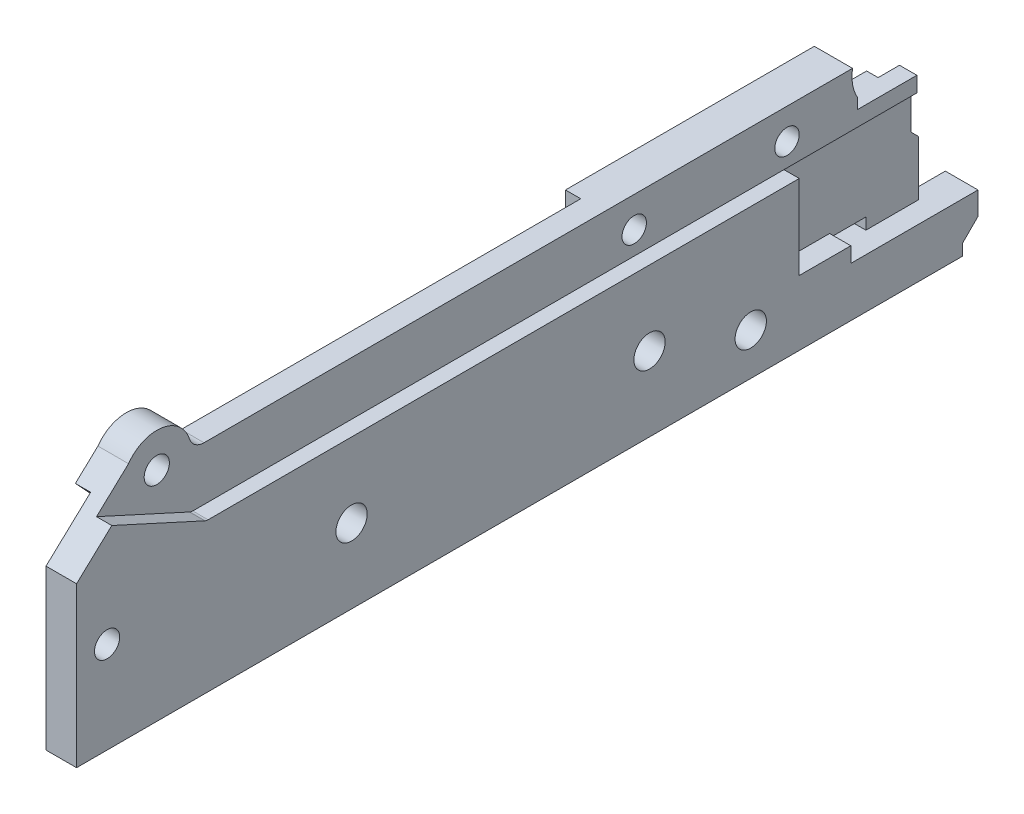
SolidWorks part; units mm, degrees
ref_plane "前视基准面" through (0, 0, 0) normal (0, 0, 1) x (1, 0, 0)
ref_plane "上视基准面" through (0, 0, 0) normal (0, 1, 0) x (1, 0, 0)
ref_plane "右视基准面" through (0, 0, 0) normal (1, 0, 0) x (0, 0, -1)
other "Configuration Table"
sketch "草图1" plane through (0, 0, 0) normal (1, 0, 0) x (0, 0, -1)
  line L0 (0, 0) -> (20, 0) construction
  line L2 (29.2, 6.5) -> (-4, 6.5)
  line L3 (29.2, 6.5) -> (29.2, -15.5)
  line L4 (29.2, -15.5) -> (-4, -15.5)
  line L5 (-4, 6.5) -> (-4, -15.5)
  circle A0 centre (0, 0) radius 1.6
  circle A1 centre (20, 0) radius 1.6
  dimension "D1" = 20
  dimension "D2" = 3.2
  dimension "D4" = 9.2
  dimension "D6" = 4
  dimension "D3" = 6.5
  dimension "D5" = 22
extrude "凸台-拉伸1" add sketch "草图1" along normal blind 7
sketch "草图2" plane through (7, 0, 0) normal (1, 0, 0) x (0, 0, -1)
  line L1 (-4, 6.5) -> (29.2, 6.5)
  line L2 (-4, 6.5) -> (-4, 17)
  line L3 (-4, 17) -> (29.2, 17)
  line L4 (29.2, 6.5) -> (29.2, 17)
  dimension "D1" = 10.5
extrude "凸台-拉伸2" add sketch "草图2" against normal offset from surface (2 mm away) 5 up to face at (0, 0, -1.6)
sketch "草图3" plane through (0, 0, 4) normal (0, 0, 1) x (1, 0, 0)
  line L1 (7, -15.5) -> (1, -15.5)
  line L2 (7, -15.5) -> (7, 6.5)
  line L3 (7, 6.5) -> (3, 6.5)
  line L4 (1, -15.5) -> (1, 4.5)
  line L5 (3, 6.5) -> (3, 4.5)
  line L6 (3, 4.5) -> (1, 4.5)
  line L7 (5, 6.5) -> (0, 6.5) construction
  dimension "D1" = 6
  dimension "D2" = 2
  dimension "D3" = 2
extrude "凸台-拉伸3" add sketch "草图3" along normal blind 60
sketch "草图4" plane through (0, 0, 4) normal (0, 0, 1) x (1, 0, 0)
  line L4 (5, 6.5) -> (7, 6.5)
  line L5 (7, 6.5) -> (7, 17)
  line L6 (7, 17) -> (5, 17)
  line L7 (5, 17) -> (5, 6.5)
  line L8 (5, 6.5) -> (7, 6.5)
  line L9 (7, 6.5) -> (7, 17)
  line L10 (7, 17) -> (5, 17)
  line L11 (5, 17) -> (5, 6.5)
  dimension "D1" = 0
extrude "凸台-拉伸4" add sketch "草图4" along normal blind 38.5
sketch "草图5" plane through (0, 0, 42.5) normal (0, 0, 1) x (1, 0, 0)
  line L0 (7, 6.5) -> (7, 17) construction
  line L1 (7, 6.5) -> (3, 6.5)
  line L2 (7, 6.5) -> (7, 17)
  line L3 (7, 17) -> (3, 17)
  line L4 (3, 6.5) -> (3, 17)
  line L5 (7, 17) -> (5, 17) construction
extrude "凸台-拉伸5" add sketch "草图5" along normal blind 2
sketch "草图6" plane through (0, 0, 44.5) normal (0, 0, 1) x (1, 0, 0)
  line L4 (7, 6.5) -> (7, 17)
  line L5 (7, 17) -> (3, 17)
  line L6 (3, 17) -> (3, 6.5)
  line L7 (3, 6.5) -> (7, 6.5)
  line L8 (7, 6.5) -> (7, 17)
  line L9 (7, 17) -> (3, 17)
  line L10 (3, 17) -> (3, 6.5)
  line L11 (3, 6.5) -> (7, 6.5)
  dimension "D1" = 0
extrude "凸台-拉伸6" add sketch "草图6" along normal up to surface (19.5 mm away) up to face at (3.6667, -1.5, 64)
sketch "草图7" plane through (0, 17, 0) normal (0, 1, 0) x (1, 0, 0)
  line L0 (1, -64) -> (1, -4) construction
  line L1 (7, 29.2) -> (1, 29.2)
  line L2 (7, 29.2) -> (7, -64)
  line L3 (7, -64) -> (1, -64)
  line L4 (1, 29.2) -> (1, -64)
  line L5 (7, -64) -> (3, -64) construction
extrude "凸台-拉伸7" add sketch "草图7" along normal blind 2
sketch "草图8" plane through (1, 0, 0) normal (-1, 0, 0) x (0, 0, 1)
  line L1 (-29.2, 19) -> (64, 19)
  line L2 (-29.2, 19) -> (-29.2, 24)
  line L3 (-29.2, 24) -> (64, 24)
  line L4 (64, 19) -> (64, 24)
  dimension "D1" = 5
extrude "凸台-拉伸8" add sketch "草图8" against normal blind 3
sketch "草图10" plane through (1, 0, 0) normal (-1, 0, 0) x (0, 0, 1)
  line L1 (-29.2, 24) -> (64, 24)
  line L2 (-29.2, 24) -> (-29.2, 22)
  line L3 (-29.2, 22) -> (64, 22)
  line L4 (64, 24) -> (64, 22)
  line L5 (64, 24) -> (64, 17) construction
  dimension "D1" = 2
extrude "凸台-拉伸9" add sketch "草图10" along normal blind 5.5
sketch "草图12" plane through (-4.5, 0, 0) normal (-1, 0, 0) x (0, 0, 1)
  line L0 (64, 24) -> (-29.2, 24) construction
  line L1 (-29.2, 22) -> (-11.2, 22)
  line L2 (-29.2, 22) -> (-29.2, 24)
  line L3 (-29.2, 24) -> (-11.2, 24)
  line L4 (-11.2, 22) -> (-11.2, 24)
  dimension "D1" = 18
extrude "切除-拉伸1" cut sketch "草图12" against normal up to surface (5.5 mm away) up to face at (1, 19.5, 17.4)
sketch "草图13" plane through (1, 0, 0) normal (-1, 0, 0) x (0, 0, 1)
  line L0 (-11.2, 22) -> (64, 22) construction
  line L1 (10.8, 22) -> (-29.2, 22)
  line L2 (10.8, 22) -> (10.8, 17)
  line L3 (10.8, 17) -> (-29.2, 17)
  line L4 (-29.2, 22) -> (-29.2, 17)
  dimension "D1" = 40
extrude "凸台-拉伸10" add sketch "草图13" along normal blind 3.5
sketch "草图14" plane through (-2.5, 0, 0) normal (-1, 0, 0) x (0, 0, 1)
  line L0 (-29.2, 17) -> (10.8, 17) construction
  line L1 (-11.2, 19.8) -> (-9.2, 19.8)
  line L2 (-11.2, 19.8) -> (-11.2, 17)
  line L3 (-11.2, 17) -> (-9.2, 17)
  line L4 (-9.2, 19.8) -> (-9.2, 17)
  line L5 (10.8, 22) -> (-11.2, 22) construction
  line L6 (-11.2, 22) -> (-11.2, 24) construction
  dimension "D1" = 2
  dimension "D2" = 2.2
sketch "草图15" plane through (4, 0, 0) normal (1, 0, 0) x (0, 0, -1)
  line L0 (29.2, 19) -> (-64, 19) construction
  line L1 (29.2, 24) -> (13.7, 24)
  line L2 (29.2, 24) -> (29.2, 19)
  line L3 (29.2, 19) -> (13.7, 19)
  line L4 (13.7, 24) -> (13.7, 19)
  line L6 (11.2, 22) -> (11.2, 24) construction
  dimension "D1" = 2.5
extrude "切除-拉伸2" cut sketch "草图15" against normal up to next
sketch "草图16" plane through (0, 22, 0) normal (0, 1, 0) x (1, 0, 0)
  line L4 (1, 11.2) -> (1, 13.7)
  line L5 (1, 13.7) -> (-2.5, 13.7)
  line L6 (-2.5, 13.7) -> (-2.5, 11.2)
  line L7 (-2.5, 11.2) -> (1, 11.2)
  line L8 (1, 11.2) -> (1, 13.7)
  line L9 (1, 13.7) -> (-2.5, 13.7)
  line L10 (-2.5, 13.7) -> (-2.5, 11.2)
  line L11 (-2.5, 11.2) -> (1, 11.2)
  dimension "D1" = 0
extrude "凸台-拉伸12" add sketch "草图16" along normal up to surface (2 mm away) up to face at (0.1667, 24, 13.0333)
sketch "草图17" plane through (7, 0, 0) normal (1, 0, 0) x (0, 0, -1)
  line L0 (-47.5, 24) -> (-64, 8.6135)
  line L1 (-64, 24) -> (13.7, 24) construction
  line L2 (-64, -15.5) -> (-64, 19) construction
  line L3 (-64, 8.6135) -> (-64, 24)
  line L4 (-64, 24) -> (-47.5, 24)
  dimension "D1" = 133
  dimension "D2" = 16.5
extrude "切除-拉伸3" cut sketch "草图17" against normal up to next
chamfer "倒角1" distance 3.5 angle 45 1 edges at (-4.5, 23, 48.5724)
sketch "草图18" plane through (-2.5, 0, 0) normal (-1, 0, 0) x (0, 0, 1)
  line L0 (-13.7, 19) -> (-13.7, 24) construction
  line L1 (-29.2, 19) -> (-13.7, 19) construction
  line L2 (-11.337, 27.2) -> (-11.337, 24)
  line L3 (-13.7, 24) -> (-11.2, 24) construction
  line L4 (-11.337, 24) -> (-13.7, 24)
  line L5 (-13.7, 24) -> (-13.7, 19)
  line L6 (-13.7, 19) -> (-21.337, 19)
  line L7 (-21.337, 19) -> (-21.337, 27.2)
  circle A0 centre (-16.337, 27.2) radius 1.65
  arc A1 (-11.337, 27.2) -> (-21.337, 27.2) centre (-16.337, 27.2) ccw
  dimension "D1" = 2.637
  dimension "D2" = 8.2
  dimension "D3" = 3.3
  dimension "D4" = 10
extrude "凸台-拉伸13" add sketch "草图18" against normal blind 2
fillet "圆角1" radius 2 2 edges at (-1.5, 24, -11.337) (-1.5, 19, -21.337)
sketch "草图19" plane through (0, 24, 0) normal (0, 1, 0) x (1, 0, 0)
  line L0 (-0.5, 9.337) -> (-0.5, 11.337) construction
  line L1 (4, 13.7) -> (-0.5, 13.7)
  line L2 (4, 13.7) -> (4, -7.8)
  line L3 (4, -7.8) -> (-0.5, -7.8)
  line L4 (-0.5, 13.7) -> (-0.5, -7.8)
  line L5 (-2.5, -10.8) -> (1, -10.8) construction
  dimension "D1" = 3
extrude "切除-拉伸4" cut sketch "草图19" against normal up to surface (5 mm away) up to face at (2, 19, -3.3438)
chamfer "倒角2" distance 3 angle 45 2 edges at (4, 24, 27.65) (1, 22, 30.2224)
sketch "草图20" plane through (7, 0, 0) normal (1, 0, 0) x (0, 0, -1)
  line L0 (-64, -15.5) -> (-64, 8.6135) construction
  line L1 (-64, -15.5) -> (29.2, -15.5) construction
  circle A0 centre (-62.5, 4) radius 1.65
  dimension "D1" = 1.5
  dimension "D2" = 19.5
  dimension "D3" = 3.3
extrude "切除-拉伸5" cut sketch "草图20" against normal up to next
sketch "草图21" plane through (1, 0, 0) normal (-1, 0, 0) x (0, 0, 1)
  circle A0 centre (62.5, 4) radius 1.65
  circle A1 centre (62.5, 4) radius 4.5
  dimension "D1" = 9
extrude "凸台-拉伸14" add sketch "草图21" against normal up to surface (6 mm away) up to face at (7, 3.3734, 35.3303)
sketch "草图22" plane through (1, 0, 0) normal (-1, 0, 0) x (0, 0, 1)
  line L3 (66.1986, 6.5633) -> (75, -1.6442)
  line L4 (75, -1.6442) -> (75, -15.5)
  line L5 (75, -15.5) -> (64, -15.5)
  line L6 (55.0066, 17) -> (64, 8.6135) construction
  line L7 (64, -0.2426) -> (64, -15.5)
  circle A2 centre (62.5, 4) radius 1.65 construction
  arc A3 (64, -0.2426) -> (58.0279, 4.5) centre (62.5, 4) ccw construction
  arc A4 (64, -0.2426) -> (66.1986, 6.5633) centre (62.5, 4) ccw
  dimension "D1" = 12.5
extrude "凸台-拉伸15" add sketch "草图22" against normal up to surface (6 mm away) up to face at (7, 3.3734, 36.2088)
sketch "草图23" plane through (7, 0, 0) normal (1, 0, 0) x (0, 0, -1)
  line L0 (-64, 8.6135) -> (-64.799, 7.8684)
  line L1 (-64.799, 7.8684) -> (-64, 8.2426)
  line L2 (-64, 8.2426) -> (-64, 8.6135)
  line L3 (-64, 8.6135) -> (-52.8618, 19) construction
  arc A0 (-64, 8.2426) -> (-66.1986, 6.5633) centre (-62.5, 4) ccw construction
extrude "凸台-拉伸16" add sketch "草图23" against normal up to surface (4 mm away) up to face at (3, 9.2872, 41.6414)
sketch "草图24" plane through (1, 0, 0) normal (-1, 0, 0) x (0, 0, 1)
  line L0 (75, -15.5) -> (75, -1.6442) construction
  line L1 (75, -15.5) -> (4, -15.5) construction
  circle A0 centre (71, -10.5) radius 1.65
  dimension "D1" = 3.3
  dimension "D2" = 4
  dimension "D3" = 5
extrude "切除-拉伸6" cut sketch "草图24" against normal up to next
sketch "草图25" plane through (5, 0, 0) normal (-1, 0, 0) x (0, 0, 1)
  line L0 (-29.2, 11.75) -> (42.5, 11.75) construction
  line L1 (-29.2, 6.5) -> (-29.2, 17) construction
  line L2 (42.5, 17) -> (42.5, 6.5) construction
  line L3 (17.8, 11.75) -> (-14.2, 11.75) construction
  line L4 (17.8, 8) -> (-14.2, 8)
  line L5 (17.8, 15.5) -> (-14.2, 15.5)
  arc A0 (17.8, 8) -> (17.8, 15.5) centre (17.8, 11.75) ccw
  arc A1 (-14.2, 15.5) -> (-14.2, 8) centre (-14.2, 11.75) ccw
  point P8 (1.8, 11.75)
  dimension "D1" = 47
  dimension "D2" = 15
  dimension "D3" = 7.5
extrude "切除-拉伸7" cut sketch "草图25" against normal up to next
sketch "草图26" plane through (0, 0, 42.5) normal (0, 0, -1) x (-1, 0, 0)
  line L4 (-5, 17) -> (-5, 6.5)
  line L5 (-5, 6.5) -> (-3, 6.5)
  line L6 (-3, 6.5) -> (-3, 17)
  line L7 (-3, 17) -> (-5, 17)
  line L8 (-5, 17) -> (-5, 6.5)
  line L9 (-5, 6.5) -> (-3, 6.5)
  line L10 (-3, 6.5) -> (-3, 17)
  line L11 (-3, 17) -> (-5, 17)
  dimension "D1" = 0
extrude "切除-拉伸8" cut sketch "草图26" against normal blind 5
sketch "草图27" plane through (0, 0, 4) normal (0, 0, 1) x (1, 0, 0)
  line L1 (1, 4.5) -> (3, 4.5)
  line L2 (1, 4.5) -> (1, 6.5)
  line L3 (1, 6.5) -> (3, 6.5)
  line L4 (3, 4.5) -> (3, 6.5)
extrude "凸台-拉伸17" add sketch "草图27" along normal blind 10
sketch "草图28" plane through (1, 0, 0) normal (-1, 0, 0) x (0, 0, 1)
  line L0 (67, 1.4943) -> (67, -15.5)
  line L2 (75, -15.5) -> (4, -15.5) construction
  line L3 (67, -15.5) -> (75, -15.5)
  line L4 (75, -15.5) -> (75, -1.6442)
  line L5 (75, -1.6442) -> (69.1556, 3.8058)
  line L6 (69.1556, 3.8058) -> (67, 1.4943)
  line L7 (75, -1.6442) -> (66.1986, 6.5633) construction
  circle A0 centre (62.5, 4) radius 1.65 construction
  dimension "D3" = 5
  dimension "D1" = 8
  dimension "D2" = 137
extrude "切除-拉伸9" cut sketch "草图28" against normal blind 2
sketch "草图29" plane through (7, 0, 0) normal (1, 0, 0) x (0, 0, -1)
  circle A0 centre (34, 3.1) radius 5.5
  circle A1 centre (20, 0) radius 1.6 construction
  dimension "D1" = 3.1
  dimension "D2" = 14
  dimension "D3" = 11
extrude "切除-拉伸10" cut sketch "草图29" against normal up to next
sketch "草图30" plane through (1, 0, 0) normal (-1, 0, 0) x (0, 0, 1)
  line L0 (4, 6.5) -> (4, -15.5) construction
  line L1 (4, -4.5) -> (67, -4.5)
  line L2 (4, -4.5) -> (4, -6.5)
  line L3 (4, -6.5) -> (67, -6.5)
  line L4 (67, -4.5) -> (67, -6.5)
  line L5 (67, 1.4943) -> (67, -15.5) construction
  circle A0 centre (0, 0) radius 1.6 construction
  dimension "D1" = 4.5
  dimension "D2" = 2
extrude "凸台-拉伸18" add sketch "草图30" along normal up to surface (1 mm away) up to face at (0, -1.9667, -18.0167)
sketch "草图31" plane through (5, 0, 0) normal (-1, 0, 0) x (0, 0, 1)
  line L0 (-14.2, 8) -> (17.8, 8) construction
  line L1 (17.8, 15.5) -> (-14.2, 15.5) construction
  line L2 (-14.2, 8) -> (17.8, 8)
  line L3 (17.8, 15.5) -> (-14.2, 15.5)
  line L4 (-29.2, 6.5) -> (47.5, 6.5)
  line L5 (47.5, 6.5) -> (47.5, 17)
  line L6 (47.5, 17) -> (-29.2, 17)
  line L7 (-29.2, 17) -> (-29.2, 6.5)
  line L8 (-29.2, 6.5) -> (47.5, 6.5)
  line L9 (47.5, 6.5) -> (47.5, 17)
  line L10 (47.5, 17) -> (-29.2, 17)
  line L11 (-29.2, 17) -> (-29.2, 6.5)
  arc A0 (17.8, 8) -> (17.8, 15.5) centre (17.8, 11.75) ccw construction
  arc A1 (-14.2, 15.5) -> (-14.2, 8) centre (-14.2, 11.75) ccw construction
  arc A2 (17.8, 8) -> (17.8, 15.5) centre (17.8, 11.75) ccw
  arc A3 (-14.2, 15.5) -> (-14.2, 8) centre (-14.2, 11.75) ccw
  dimension "D1" = 0
sketch "草图32" plane through (-2.5, 0, 0) normal (-1, 0, 0) x (0, 0, 1)
  line L8 (-11.2, 22) -> (-11.2, 25.2725)
  line L9 (-11.337, 26) -> (-11.337, 27.2)
  line L10 (-21.337, 27.2) -> (-21.337, 21)
  line L11 (-23.337, 19) -> (-29.2, 19)
  line L12 (-29.2, 19) -> (-29.2, 17)
  line L13 (-29.2, 17) -> (10.8, 17)
  line L14 (10.8, 17) -> (10.8, 22)
  line L15 (10.8, 22) -> (-11.2, 22)
  line L16 (-11.2, 22) -> (-11.2, 25.2725)
  line L17 (-11.337, 26) -> (-11.337, 27.2)
  line L18 (-21.337, 27.2) -> (-21.337, 21)
  line L19 (-23.337, 19) -> (-29.2, 19)
  line L20 (-29.2, 19) -> (-29.2, 17)
  line L21 (-29.2, 17) -> (10.8, 17)
  line L22 (10.8, 17) -> (10.8, 22)
  line L23 (10.8, 22) -> (-11.2, 22)
  circle A0 centre (-16.337, 27.2) radius 1.65 construction
  circle A1 centre (-16.337, 27.2) radius 1.65
  arc A3 (-11.337, 26) -> (-11.2, 25.2725) centre (-9.337, 26) ccw
  arc A4 (-11.337, 27.2) -> (-21.337, 27.2) centre (-16.337, 27.2) ccw
  arc A5 (-23.337, 19) -> (-21.337, 21) centre (-23.337, 21) ccw
  arc A6 (-11.337, 26) -> (-11.2, 25.2725) centre (-9.337, 26) ccw
  arc A7 (-11.337, 27.2) -> (-21.337, 27.2) centre (-16.337, 27.2) ccw
  arc A8 (-23.337, 19) -> (-21.337, 21) centre (-23.337, 21) ccw
  dimension "D1" = 0
extrude "凸台-拉伸19" add sketch "草图32" along normal blind 0.775
sketch "草图34" plane through (0, -15.5, 0) normal (0, -1, 0) x (1, 0, 0)
  line L8 (3, 75) -> (3, 67)
  line L9 (3, 67) -> (1, 67)
  line L10 (1, 67) -> (1, 4)
  line L11 (1, 4) -> (0, 4)
  line L12 (0, 4) -> (0, -29.2)
  line L13 (0, -29.2) -> (7, -29.2)
  line L14 (7, -29.2) -> (7, 75)
  line L15 (7, 75) -> (3, 75)
  line L16 (3, 75) -> (3, 67)
  line L17 (3, 67) -> (1, 67)
  line L18 (1, 67) -> (1, 4)
  line L19 (1, 4) -> (0, 4)
  line L20 (0, 4) -> (0, -29.2)
  line L21 (0, -29.2) -> (7, -29.2)
  line L22 (7, -29.2) -> (7, 75)
  line L23 (7, 75) -> (3, 75)
  dimension "D1" = 0
extrude "凸台-拉伸20" add sketch "草图34" along normal blind 5.5
sketch "草图35" plane through (0, 0, 0) normal (-1, 0, 0) x (0, 0, 1)
  line L1 (-24.2, -11) -> (-29.2, -11)
  line L2 (-24.2, -11) -> (-24.2, -21)
  line L3 (-24.2, -21) -> (-29.2, -21)
  line L4 (-29.2, -11) -> (-29.2, -21)
  dimension "D1" = 5
  dimension "D2" = 10
extrude "切除-拉伸12" cut sketch "草图35" against normal blind 1.225
sketch "草图36" plane through (0, 0, -29.2) normal (0, 0, -1) x (-1, 0, 0)
  line L1 (-1.225, -21) -> (-5.225, -21)
  line L2 (-1.225, -21) -> (-1.225, -11)
  line L3 (-1.225, -11) -> (-5.225, -11)
  line L4 (-5.225, -21) -> (-5.225, -11)
  dimension "D1" = 10
  dimension "D2" = 4
extrude "凸台-拉伸21" add sketch "草图36" along normal blind 5
sketch "草图37" plane through (5.225, 0, 0) normal (1, 0, 0) x (0, 0, -1)
  line L0 (34.2, -11) -> (34.2, -21) construction
  line L1 (33.6, -16) -> (28.85, -16)
  line L2 (33.6, -16) -> (33.6, -13)
  line L3 (33.6, -13) -> (28.85, -13)
  line L4 (28.85, -16) -> (28.85, -13)
  line L5 (34.2, -21) -> (29.2, -21) construction
  dimension "D1" = 5
  dimension "D2" = 3
  dimension "D3" = 5.35
  dimension "D4" = 0.6
extrude "切除-拉伸13" cut sketch "草图37" against normal up to next and the other way up to next
sketch "草图38" plane through (5.225, 0, 0) normal (1, 0, 0) x (0, 0, -1)
  line L0 (34.2, -11) -> (34.2, -21) construction
  line L1 (34.2, -14) -> (19.6, -14)
  line L2 (34.2, -14) -> (34.2, -3)
  line L3 (34.2, -3) -> (19.6, -3)
  line L4 (19.6, -14) -> (19.6, -3)
  line L5 (33.6, -16) -> (29.2, -16) construction
  line L7 (28.85, -16) -> (28.85, -13) construction
  dimension "D1" = 2
  dimension "D2" = 9.25
  dimension "D3" = 11
extrude "切除-拉伸14" cut sketch "草图38" along normal up to next and the other way blind 1
sketch "草图39" plane through (0, 0, -34.2) normal (0, 0, -1) x (-1, 0, 0)
  line L1 (-2.725, -1) -> (-4.225, -1)
  line L2 (-2.725, -1) -> (-2.725, -21)
  line L3 (-2.725, -21) -> (-4.225, -21)
  line L4 (-4.225, -1) -> (-4.225, -21)
  line L5 (-5.225, -21) -> (-1.225, -21) construction
  line L6 (-5.225, -14) -> (-5.225, -21) construction
  line L7 (-1.225, -11) -> (0, -11) construction
  dimension "D1" = 2.5
  dimension "D2" = 1
  dimension "D3" = 10
extrude "凸台-拉伸22" add sketch "草图39" along normal blind 5.8 and the other way up to next
sketch "草图40" plane through (0, 0, -29.2) normal (0, 0, -1) x (-1, 0, 0)
  line L1 (-1.225, -11) -> (-2.725, -11)
  line L2 (-1.225, -11) -> (-1.225, -1)
  line L3 (-1.225, -1) -> (-2.725, -1)
  line L4 (-2.725, -11) -> (-2.725, -1)
extrude "凸台-拉伸23" add sketch "草图40" along normal up to surface (5 mm away) up to face at (1.975, -16, -34.2)
sketch "草图41" plane through (4.225, 0, 0) normal (1, 0, 0) x (0, 0, -1)
  line L1 (40, -1) -> (39, -1)
  line L2 (40, -1) -> (40, -8)
  line L3 (40, -8) -> (39, -8)
  line L4 (39, -1) -> (39, -8)
  dimension "D1" = 1
  dimension "D2" = 7
extrude "切除-拉伸15" cut sketch "草图41" against normal up to next
chamfer "倒角3" distance 1 angle 45 1 edges at (3.475, -8, -39)
sketch "草图42" plane through (0, 0, -29.2) normal (0, 0, -1) x (-1, 0, 0)
  line L1 (-4.225, -21) -> (-7, -21)
  line L2 (-4.225, -21) -> (-4.225, -16)
  line L3 (-4.225, -16) -> (-7, -16)
  line L4 (-7, -21) -> (-7, -16)
extrude "凸台-拉伸24" add sketch "草图42" along normal up to surface (10.8 mm away) up to face at (3.475, -14.5, -40)
sketch "草图43" plane through (4.225, 0, 0) normal (1, 0, 0) x (0, 0, -1)
  line L4 (33.6, -16) -> (34.2, -16)
  line L5 (34.2, -16) -> (34.2, -14)
  line L6 (34.2, -14) -> (33.6, -14)
  line L7 (33.6, -14) -> (33.6, -16)
  line L8 (33.6, -16) -> (34.2, -16)
  line L9 (34.2, -16) -> (34.2, -14)
  line L10 (34.2, -14) -> (33.6, -14)
  line L11 (33.6, -14) -> (33.6, -16)
  dimension "D1" = 0
extrude "切除-拉伸16" cut sketch "草图43" along normal up to next
sketch "草图44" plane through (4.225, 0, 0) normal (1, 0, 0) x (0, 0, -1)
  line L1 (29.2, -3) -> (39, -3)
  line L2 (29.2, -3) -> (29.2, -1)
  line L3 (29.2, -1) -> (39, -1)
  line L4 (39, -3) -> (39, -1)
extrude "凸台-拉伸25" add sketch "草图44" along normal offset from surface (2 mm away) 0.775 up to face at (7, 0, -21.6)
sketch "草图45" plane through (7, 0, 0) normal (1, 0, 0) x (0, 0, -1)
  line L0 (39, -3) -> (19.6, -3) construction
  line L1 (28.5, 3.1) -> (29.3, 3.1)
  line L2 (28.5, 3.1) -> (28.5, -3)
  line L3 (28.5, -3) -> (29.3, -3)
  line L4 (29.3, 3.1) -> (29.3, -3)
  arc A0 (29.2, 5.7851) -> (29.2, 0.4149) centre (34, 3.1) ccw construction
extrude "切除-拉伸17" cut sketch "草图45" against normal up to surface (0.775 mm away) up to face at (6.225, -2, -34.1)
sketch "草图46" plane through (7, 0, 0) normal (1, 0, 0) x (0, 0, -1)
  circle A0 centre (13.25, -17) radius 2.05
  circle A1 centre (20, 0) radius 1.6 construction
  dimension "D1" = 17
  dimension "D2" = 6.75
  dimension "D3" = 4.1
extrude "切除-拉伸18" cut sketch "草图46" against normal up to next
sketch "草图47" plane through (1, 0, 0) normal (-1, 0, 0) x (0, 0, 1)
  line L0 (62.5, -0.5) -> (67, -0.5)
  line L8 (4, -4.5) -> (67, -4.5)
  line L9 (67, -4.5) -> (67, 1.4943)
  line L10 (67, 1.4943) -> (69.1556, 3.8058)
  line L11 (69.1556, 3.8058) -> (66.1986, 6.5633)
  line L12 (58.0279, 4.5) -> (14, 4.5)
  line L13 (14, 4.5) -> (14, 6.5)
  line L14 (14, 6.5) -> (4, 6.5)
  line L15 (4, 6.5) -> (4, -4.5)
  line L16 (4, -4.5) -> (67, -4.5)
  line L17 (67, -4.5) -> (67, -0.5)
  line L20 (58.0279, 4.5) -> (14, 4.5)
  line L21 (14, 4.5) -> (14, 6.5)
  line L22 (14, 6.5) -> (4, 6.5)
  line L23 (4, 6.5) -> (4, -4.5)
  arc A0 (58.0279, 4.5) -> (62.5, -0.5) centre (62.5, 4) ccw
  arc A1 (66.1986, 6.5633) -> (58.0279, 4.5) centre (62.5, 4) ccw
  dimension "D1" = 0
extrude "切除-拉伸19" cut sketch "草图47" against normal blind 1
sketch "草图48" plane through (0, -21, 0) normal (0, -1, 0) x (1, 0, 0)
  line L0 (0, 58) -> (7, 58) construction
  line L1 (3.5, 58) -> (3.5, -18) construction
  line L2 (7, -40) -> (7, 75) construction
  line L3 (7, 75) -> (3, 75) construction
  line L4 (0, 4) -> (0, 67) construction
  circle A0 centre (3.5, 58) radius 2.05
  circle A1 centre (3.5, 20) radius 2.05
  circle A2 centre (3.5, -18) radius 2.05
  dimension "D1" = 4.1
  dimension "D3" = 38
  dimension "D4" = 38
  dimension "D2" = 17
extrude "切除-拉伸20" cut sketch "草图48" against normal blind 5
sketch "草图50" plane through (0, 0, 67) normal (0, 0, 1) x (1, 0, 0)
  line L0 (0, -21) -> (0, -3.5)
  line L2 (0, -3.5) -> (0.5, -3.5)
  line L3 (0.5, -3.5) -> (0.5, -21)
  line L5 (0.5, -21) -> (0, -21)
  line L7 (0, 6.5) -> (0, -4.5) construction
  line L8 (0, -4.5) -> (2, -4.5) construction
  dimension "D1" = 0.5
  dimension "D2" = 1
extrude "切除-拉伸21" cut sketch "草图50" against normal up to next
sketch "草图51" plane through (0, 0, -28.85) normal (0, 0, -1) x (-1, 0, 0)
  line L6 (-4.225, -14) -> (-7, -14)
  line L7 (-7, -14) -> (-7, -16)
  line L8 (-7, -16) -> (-1.225, -16)
  line L9 (-1.225, -16) -> (-1.225, -13)
  line L10 (-1.225, -13) -> (-4.225, -13)
  line L11 (-4.225, -13) -> (-4.225, -14)
  line L12 (-4.225, -14) -> (-7, -14)
  line L13 (-7, -14) -> (-7, -16)
  line L14 (-7, -16) -> (-1.225, -16)
  line L15 (-1.225, -16) -> (-1.225, -13)
  line L16 (-1.225, -13) -> (-4.225, -13)
  line L17 (-4.225, -13) -> (-4.225, -14)
  dimension "D1" = 0
extrude "切除-拉伸22" cut sketch "草图51" against normal blind 3
sketch "草图52" plane through (0, -21, 0) normal (0, -1, 0) x (1, 0, 0)
  line L0 (1, 59.6583) -> (1, 56.3417)
  line L1 (1, 67) -> (1, 4) construction
  line L2 (1, 21.6583) -> (1, 18.3417)
  arc A0 (1, 59.6583) -> (1, 56.3417) centre (3.5, 58) ccw
  arc A1 (1, 21.6583) -> (1, 18.3417) centre (3.5, 20) ccw
  circle A3 centre (3.5, 20) radius 2.05 construction
  dimension "D1" = 6
extrude "凸台-拉伸26" add sketch "草图52" against normal up to surface (14.5 mm away) up to face at (0.75, -6.5, 35.5)
sketch "草图53" plane through (1, 0, 0) normal (-1, 0, 0) x (0, 0, 1)
  line L0 (67, 1.4943) -> (67, -21) construction
  line L2 (4, -21) -> (4, -19)
  line L3 (4, -19) -> (18.3417, -19)
  line L4 (67, -21) -> (67, -19)
  line L5 (21.6583, -19) -> (56.3417, -19)
  line L6 (56.3417, -6.5) -> (59.6583, -6.5)
  line L7 (56.3417, -6.5) -> (56.3417, -19)
  line L9 (59.6583, -6.5) -> (59.6583, -19)
  line L10 (18.3417, -6.5) -> (21.6583, -6.5)
  line L11 (18.3417, -6.5) -> (18.3417, -19)
  line L13 (21.6583, -6.5) -> (21.6583, -19)
  line L14 (59.6583, -19) -> (66, -19)
  line L15 (59.6583, -6.5) -> (59.6583, -21) construction
  line L16 (21.6583, -6.5) -> (21.6583, -21) construction
  line L17 (4, -21) -> (67, -21)
  line L18 (67, -6.5) -> (67, -4.5) construction
  line L19 (67, -6.5) -> (66, -6.5)
  line L20 (67, -6.5) -> (67, -19)
  line L22 (66, -6.5) -> (66, -19)
  line L23 (59.6583, -6.5) -> (67, -6.5) construction
  dimension "D1" = 2
  dimension "D2" = 1
extrude "凸台-拉伸27" add sketch "草图53" along normal up to surface (0.5 mm away) up to face at (0.5, -8.8333, 10.1)
sketch "草图54" plane through (1, 0, 0) normal (-1, 0, 0) x (0, 0, 1)
  line L0 (21.6583, -6.5) -> (56.3417, -6.5) construction
  line L1 (24.6583, -6.5) -> (53.3417, -6.5)
  line L2 (24.6583, -6.5) -> (24.6583, -19)
  line L3 (24.6583, -19) -> (53.3417, -19)
  line L4 (53.3417, -6.5) -> (53.3417, -19)
  line L5 (21.6583, -19) -> (56.3417, -19) construction
  line L6 (18.3417, -6.5) -> (18.3417, -19) construction
  line L7 (4, -6.5) -> (15.3417, -6.5)
  line L8 (4, -6.5) -> (4, -19)
  line L9 (4, -19) -> (15.3417, -19)
  line L10 (15.3417, -6.5) -> (15.3417, -19)
  line L11 (4, -19) -> (18.3417, -19) construction
  line L12 (21.6583, -6.5) -> (21.6583, -19) construction
  line L13 (56.3417, -6.5) -> (56.3417, -19) construction
  dimension "D1" = 3
  dimension "D2" = 3
  dimension "D3" = 3
extrude "切除-拉伸23" cut sketch "草图54" against normal blind 3
sketch "草图55" plane through (0.5, 0, 0) normal (-1, 0, 0) x (0, 0, 1)
  line L0 (4, -18.3367) -> (17.5807, -6.5)
  line L1 (4, -19) -> (4, -6.5) construction
  line L2 (15.3417, -6.5) -> (18.3417, -6.5) construction
  line L3 (4, -19) -> (18.3417, -6.5) construction
  line L4 (21.6583, -6.5) -> (56.3417, -19) construction
  line L5 (66, -19) -> (59.6583, -6.5) construction
  line L6 (56.3417, -6.5) -> (21.6583, -19) construction
  line L7 (18.3417, -7.1633) -> (4.761, -19)
  line L8 (18.3417, -19) -> (18.3417, -6.5) construction
  line L9 (4, -19) -> (15.3417, -19) construction
  line L10 (17.5807, -6.5) -> (18.3417, -6.5)
  line L11 (18.3417, -6.5) -> (18.3417, -7.1633)
  line L12 (4, -18.3367) -> (4, -19)
  line L13 (4, -19) -> (4.761, -19)
  line L14 (23.133, -6.5) -> (39, -12.2185)
  line L15 (21.6583, -6.5) -> (24.6583, -6.5) construction
  line L16 (56.3417, -19) -> (56.3417, -6.5) construction
  line L17 (54.867, -19) -> (39, -13.2815)
  line L18 (21.6583, -19) -> (56.3417, -19) construction
  line L19 (21.6583, -6.5) -> (21.6583, -19) construction
  line L20 (21.6583, -18.4685) -> (37.5253, -12.75)
  line L21 (21.6583, -6.5) -> (56.3417, -6.5) construction
  line L22 (23.133, -19) -> (39, -13.2815)
  line L23 (39, -12.2185) -> (54.867, -6.5)
  line L24 (40.4747, -12.75) -> (56.3417, -18.4685)
  line L25 (37.5253, -12.75) -> (21.6583, -7.0315)
  line L26 (40.4747, -12.75) -> (56.3417, -7.0315)
  line L27 (23.133, -6.5) -> (21.6583, -6.5)
  line L28 (21.6583, -6.5) -> (21.6583, -7.0315)
  line L29 (54.867, -6.5) -> (56.3417, -6.5)
  line L30 (56.3417, -6.5) -> (56.3417, -7.0315)
  line L31 (56.3417, -18.4685) -> (56.3417, -19)
  line L32 (56.3417, -19) -> (54.867, -19)
  line L33 (23.133, -19) -> (21.6583, -19)
  line L34 (21.6583, -19) -> (21.6583, -18.4685)
  line L35 (59.6583, -7.6051) -> (65.4393, -19)
  line L36 (59.6583, -6.5) -> (59.6583, -19) construction
  line L37 (59.6583, -19) -> (66, -19) construction
  line L38 (60.219, -6.5) -> (66, -17.8949)
  line L39 (59.6583, -6.5) -> (66, -6.5) construction
  line L40 (66, -6.5) -> (66, -19) construction
  line L41 (59.6583, -7.6051) -> (59.6583, -6.5)
  line L42 (59.6583, -6.5) -> (60.219, -6.5)
  line L43 (66, -17.8949) -> (66, -19)
  line L44 (66, -19) -> (65.4393, -19)
  dimension "D1" = 1
  dimension "D2" = 1
  dimension "D3" = 1
  dimension "D4" = 1
extrude "凸台-拉伸28" add sketch "草图55" against normal up to next
fillet "圆角2" radius 0.8 30 edges at (0.75, -19, 18.3417) (2.5, -19, 15.3417) (2.5, -6.5, 15.3417) (2.25, -6.5, 4) (0.75, -7.1633, 18.3417) (0.75, -6.5, 17.5807) (2.5, -9.778, 15.3417) (2.5, -8.4515, 15.3417) (2.25, -18.3367, 4) (2.25, -19, 4.761) (2.25, -12.75, 37.5253) (2.25, -13.2815, 39) (2.25, -12.2185, 39) (2.25, -12.75, 40.4747) (2.5, -8.1127, 53.3417) (2.5, -17.3873, 53.3417) (0.75, -18.4685, 56.3417) (0.75, -7.0315, 56.3417) (0.75, -6.5, 54.867) (0.75, -19, 54.867) (0.75, -19, 23.133) (0.75, -6.5, 23.133) (0.75, -18.4685, 21.6583) (0.75, -7.0315, 21.6583) (0.75, -17.8949, 66) (0.75, -19, 59.6583) (0.75, -19, 65.4393) (0.75, -6.5, 66) (0.75, -6.5, 60.219) (0.75, -7.6051, 59.6583)
sketch "草图56" plane through (0.5, 0, 0) normal (-1, 0, 0) x (0, 0, 1)
  line L0 (35.9658, -12.75) -> (42.0342, -12.75) construction
  line L1 (39, -12.1681) -> (39, -13.3319) construction
  arc A0 (35.4371, -13.5026) -> (35.4371, -11.9974) centre (35.1658, -12.75) ccw construction
  arc A1 (42.5629, -11.9974) -> (42.5629, -13.5026) centre (42.8342, -12.75) ccw construction
  arc A2 (38.7288, -12.1208) -> (39.2712, -12.1208) centre (39, -11.3681) ccw construction
  arc A3 (39.2712, -13.3792) -> (38.7288, -13.3792) centre (39, -14.1319) ccw construction
  circle A4 centre (39, -12.75) radius 2.05
  circle A5 centre (39, -12.75) radius 4
  dimension "D1" = 4.1
  dimension "D2" = 8
extrude "凸台-拉伸29" add sketch "草图56" against normal up to next (3.5 mm away)
fillet "圆角3" radius 0.8 8 edges at (2.25, -14.566, 35.436) (2.25, -14.566, 42.564) (2.25, -13.6252, 42.9031) (2.25, -11.8748, 42.9031) (2.25, -10.934, 42.564) (2.25, -10.934, 35.436) (2.25, -13.6252, 35.0969) (2.25, -11.8748, 35.0969)
sketch "草图57" plane through (0.5, 0, 0) normal (-1, 0, 0) x (0, 0, 1)
  line L0 (0, 0) -> (0, -12.75) construction
  line L1 (0, -12.75) -> (39, -12.75) construction
  circle A0 centre (39, -12.75) radius 2.05
  circle A1 centre (0, -12.75) radius 2.05
extrude "切除-拉伸24" cut sketch "草图57" against normal up to next
sketch "草图58" plane through (0.5, 0, 0) normal (-1, 0, 0) x (0, 0, 1)
  line L0 (-29.2, -3.5) -> (4, -3.5) construction
  line L1 (-19.2, -4.5) -> (-4, -4.5)
  line L2 (-19.2, -4.5) -> (-19.2, -13)
  line L3 (-19.2, -13) -> (-4, -13)
  line L4 (-4, -4.5) -> (-4, -13)
  line L5 (-24.2, -11) -> (-24.2, -21) construction
  circle A0 centre (-13.25, -17) radius 2.05 construction
  circle A1 centre (0, -12.75) radius 2.05 construction
  dimension "D1" = 4
  dimension "D2" = 4
  dimension "D3" = 1
  dimension "D4" = 5
extrude "切除-拉伸25" cut sketch "草图58" against normal up to surface (3.5 mm away) up to face at (4, -9.7828, 9.7862)
fillet "圆角4" radius 0.8 4 edges at (2.25, -13, -4) (2.25, -13, -19.2) (2.25, -4.5, -19.2) (2.25, -4.5, -4)
extrude "凸台-拉伸30" add sketch "草图31" along normal blind 0.5
sketch "草图59" plane through (2.725, 0, 0) normal (-1, 0, 0) x (0, 0, 1)
  line L0 (-25.85, -13) -> (-33.6, -13) construction
  line L1 (-34.2, -21) -> (-31.6, -21)
  line L2 (-34.2, -21) -> (-34.2, -11)
  line L3 (-34.2, -11) -> (-31.6, -11)
  line L4 (-31.6, -21) -> (-31.6, -11)
  line L5 (-33.6, -13) -> (-33.6, -16) construction
  dimension "D1" = 2
  dimension "D2" = 2
extrude "切除-拉伸26" cut sketch "草图59" along normal up to next
sketch "草图60" plane through (2.725, 0, 0) normal (-1, 0, 0) x (0, 0, 1)
  line L0 (-37, -1) -> (-37, -7.8284)
  line L1 (-34.2, -1) -> (-39, -1) construction
  line L2 (-37, -7.8284) -> (-38, -8.8284)
  line L4 (-38, -8.8284) -> (-38, -21)
  line L5 (-40, -21) -> (-31.6, -21) construction
  line L6 (-38, -21) -> (-40, -21)
  line L7 (-40, -21) -> (-40, -8)
  line L8 (-40, -8) -> (-39, -7)
  line L9 (-39, -7) -> (-39, -1)
  line L10 (-39, -1) -> (-37, -1)
  dimension "D1" = 2
  dimension "D2" = 2
  dimension "D3" = 2
extrude "切除-拉伸27" cut sketch "草图60" against normal up to next
sketch "草图61" plane through (4.225, 0, 0) normal (1, 0, 0) x (0, 0, -1)
  line L0 (32.6, -16) -> (32.6, -14.5)
  line L1 (38, -16) -> (25.85, -16) construction
  line L2 (32.6, -14.5) -> (27.35, -14.5)
  line L3 (27.35, -14.5) -> (27.35, -16)
  line L4 (27.35, -16) -> (25.85, -16)
  line L5 (25.85, -16) -> (25.85, -13)
  line L6 (25.85, -13) -> (33.6, -13)
  line L7 (33.6, -13) -> (33.6, -16)
  line L8 (33.6, -16) -> (32.6, -16)
  dimension "D1" = 1.5
  dimension "D2" = 1
  dimension "D3" = 1.5
extrude "凸台-拉伸31" add sketch "草图61" against normal up to surface (1.5 mm away) up to face at (2.725, -11.7214, -34.3333)
sketch "草图62" plane through (0, 0, -25.85) normal (0, 0, -1) x (-1, 0, 0)
  line L4 (-4.225, -16) -> (-4.225, -14)
  line L5 (-4.225, -14) -> (-7, -14)
  line L6 (-7, -14) -> (-7, -16)
  line L7 (-7, -16) -> (-4.225, -16)
  line L8 (-4.225, -16) -> (-4.225, -14)
  line L9 (-4.225, -14) -> (-7, -14)
  line L10 (-7, -14) -> (-7, -16)
  line L11 (-7, -16) -> (-4.225, -16)
  dimension "D1" = 0
extrude "凸台-拉伸32" add sketch "草图62" along normal up to surface (1.5 mm away) up to face at (3.475, -15.25, -27.35)
sketch "草图63" plane through (2.725, 0, 0) normal (-1, 0, 0) x (0, 0, 1)
  line L0 (-31.6, -13) -> (-31.6, -14.5)
  line L1 (-27.35, -14.5) -> (-32.6, -14.5) construction
  line L2 (-31.6, -14.5) -> (-27.35, -14.5)
  line L3 (-27.35, -14.5) -> (-27.35, -16)
  line L4 (-27.35, -16) -> (-25.85, -16)
  line L5 (-25.85, -16) -> (-25.85, -13)
  line L6 (-25.85, -13) -> (-31.6, -13)
extrude "凸台-拉伸33" add sketch "草图63" along normal up to surface (1.5 mm away) up to face at (1.225, -12.1667, -29.4417)
sketch "草图64" plane through (0, 0, -38) normal (0, 0, -1) x (-1, 0, 0)
  line L1 (-7, -16) -> (-2.725, -16)
  line L2 (-7, -16) -> (-7, -21)
  line L3 (-7, -21) -> (-2.725, -21)
  line L4 (-2.725, -16) -> (-2.725, -21)
extrude "凸台-拉伸34" add sketch "草图64" along normal blind 5
chamfer "倒角4" distance 2 angle 45 1 edges at (4.8625, -21, -43)
sketch "草图65" plane through (0, -21, 0) normal (0, -1, 0) x (1, 0, 0)
  line L10 (2.725, -31.6) -> (2.725, -41)
  line L11 (2.725, -41) -> (7, -41)
  line L12 (7, -41) -> (7, 75)
  line L13 (7, 75) -> (3, 75)
  line L14 (3, 75) -> (3, 67)
  line L15 (3, 67) -> (0.5, 67)
  line L16 (0.5, 67) -> (0.5, -24.2)
  line L17 (0.5, -24.2) -> (1.225, -24.2)
  line L18 (1.225, -24.2) -> (1.225, -31.6)
  line L19 (1.225, -31.6) -> (2.725, -31.6)
  line L20 (2.725, -31.6) -> (2.725, -41)
  line L21 (2.725, -41) -> (7, -41)
  line L22 (7, -41) -> (7, 75)
  line L23 (7, 75) -> (3, 75)
  line L24 (3, 75) -> (3, 67)
  line L25 (3, 67) -> (0.5, 67)
  line L26 (0.5, 67) -> (0.5, -24.2)
  line L27 (0.5, -24.2) -> (1.225, -24.2)
  line L28 (1.225, -24.2) -> (1.225, -31.6)
  line L29 (1.225, -31.6) -> (2.725, -31.6)
  circle A0 centre (3.5, -18) radius 2.05 construction
  circle A1 centre (3.5, 20) radius 2.05 construction
  circle A2 centre (3.5, 58) radius 2.05 construction
  circle A3 centre (3.5, -18) radius 2.05
  circle A4 centre (3.5, 20) radius 2.05
  circle A5 centre (3.5, 58) radius 2.05
  dimension "D1" = 0
extrude "凸台-拉伸35" add sketch "草图65" along normal blind 1.5
sketch "草图66" plane through (0, 0, -27.35) normal (0, 0, -1) x (-1, 0, 0)
  line L6 (-7, -16) -> (-1.225, -16)
  line L7 (-1.225, -16) -> (-1.225, -14.5)
  line L8 (-1.225, -14.5) -> (-4.225, -14.5)
  line L9 (-4.225, -14.5) -> (-4.225, -14)
  line L10 (-4.225, -14) -> (-7, -14)
  line L11 (-7, -14) -> (-7, -16)
  line L12 (-7, -16) -> (-1.225, -16)
  line L13 (-1.225, -16) -> (-1.225, -14.5)
  line L14 (-1.225, -14.5) -> (-4.225, -14.5)
  line L15 (-4.225, -14.5) -> (-4.225, -14)
  line L16 (-4.225, -14) -> (-7, -14)
  line L17 (-7, -14) -> (-7, -16)
  dimension "D1" = 0
extrude "切除-拉伸28" cut sketch "草图66" against normal blind 1
sketch "草图67" plane through (0, 0, -32.6) normal (0, 0, 1) x (1, 0, 0)
  line L4 (4.225, -14.5) -> (2.725, -14.5)
  line L5 (2.725, -14.5) -> (2.725, -16)
  line L6 (2.725, -16) -> (4.225, -16)
  line L7 (4.225, -16) -> (4.225, -14.5)
  line L8 (4.225, -14.5) -> (2.725, -14.5)
  line L9 (2.725, -14.5) -> (2.725, -16)
  line L10 (2.725, -16) -> (4.225, -16)
  line L11 (4.225, -16) -> (4.225, -14.5)
  dimension "D1" = 0
extrude "凸台-拉伸36" add sketch "草图67" along normal blind 1.5
sketch "草图68" plane through (0, 0, 7.8) normal (0, 0, -1) x (-1, 0, 0)
  line L0 (-1, 24) -> (-4, 21)
  line L1 (-4, 21) -> (-1, 21)
  line L2 (-1, 21) -> (-1, 24)
extrude "切除-拉伸29" cut sketch "草图68" against normal up to next
sketch "草图69" plane through (0, 0, 10.8) normal (0, 0, 1) x (1, 0, 0)
  line L0 (-2, 22) -> (1, 19)
  line L1 (1, 19) -> (-2, 19)
  line L2 (-2, 19) -> (-2, 22)
extrude "凸台-拉伸37" add sketch "草图69" along normal up to surface (42.0618 mm away) up to face at (2.5, 18.1447, 53.779)
sketch "草图70" plane through (0, 24, 0) normal (0, 1, 0) x (1, 0, 0)
  line L0 (-4.5, -42.368) -> (-4.5, -52.8618)
  line L1 (-4.5, -52.8618) -> (-1, -52.8618)
  line L2 (1, -52.8618) -> (-2, -52.8618) construction
  line L3 (-1, -52.8618) -> (-1, -47.5)
  line L4 (-1, -47.5) -> (-4.5, -42.368)
extrude "切除-拉伸30" cut sketch "草图70" along direction (0, -0.682, 0.7314) on the side against the normal blind 10
sketch "草图71" plane through (-4.5, 0, 0) normal (-1, 0, 0) x (0, 0, 1)
  line L4 (-11.2, 22) -> (44.5128, 22)
  line L5 (44.5128, 22) -> (42.368, 24)
  line L6 (42.368, 24) -> (-9.337, 24)
  line L7 (-11.2, 25.2725) -> (-11.2, 22)
  line L8 (-11.2, 22) -> (44.5128, 22)
  line L9 (44.5128, 22) -> (42.368, 24)
  line L10 (42.368, 24) -> (-9.337, 24)
  line L11 (-11.2, 25.2725) -> (-11.2, 22)
  arc A1 (-11.2, 25.2725) -> (-9.337, 24) centre (-9.337, 26) ccw
  arc A2 (-11.2, 25.2725) -> (-9.337, 24) centre (-9.337, 26) ccw
  dimension "D1" = 0
extrude "凸台-拉伸38" add sketch "草图71" along normal blind 0.5
sketch "草图72" plane through (0, 24, 0) normal (0, 1, 0) x (1, 0, 0)
  line L0 (-4.5, -42.368) -> (-5, -41.6349)
  line L1 (-5, -42.368) -> (-5, 9.337) construction
  line L2 (-5, -41.6349) -> (-5, -42.368)
  line L3 (-5, -42.368) -> (-4.5, -42.368)
  line L4 (-4.5, -42.368) -> (-1, -47.5) construction
extrude "切除-拉伸31" cut sketch "草图72" along direction (0, 0.682, -0.7314) on the side against the normal up to next (2 mm away)
fillet "圆角5" radius 1 2 edges at (2.5, -17.3873, 24.6583) (2.5, -8.1127, 24.6583)
ref_plane "基准面1" through (0, 0, 58) normal (0, 0, -1) x (-1, 0, 0)
sketch "草图73" plane through (0, 0, -43) normal (0, 0, -1) x (-1, 0, 0)
  line L0 (-7, -3) -> (-6.225, -3)
  line L1 (-6.225, -3) -> (-6.225, 4)
  line L2 (-6.225, 4) -> (0, 4)
  line L3 (0, 0.4149) -> (0, 5.7851) construction
  line L4 (0, 4) -> (0, 17)
  line L5 (-4.5, 17) -> (3.275, 17) construction
  line L6 (0, 17) -> (7.1372, 17)
  line L7 (7.1372, 17) -> (7.1372, 36.0529)
  line L8 (7.1372, 36.0529) -> (-7, 36.0529)
  line L9 (-7, 36.0529) -> (-7, -3)
  point P4 (0, 0)
  point P16 (-6.225, 3.1)
  point P17 (-7.1383, -3)
  dimension "D1" = 4
  dimension "D2" = 7.1372
  dimension "D3" = 19.0529
extrude "切除-拉伸32" cut sketch "草图73" against normal up to surface (101 mm away) up to plane "基准面1"
sketch "草图74" plane through (3, 0, 0) normal (-1, 0, 0) x (0, 0, 1)
  line L3 (58, 14.2086) -> (58, 4.5)
  line L4 (58, 4.5) -> (58.0279, 4.5)
  line L5 (64.799, 7.8684) -> (58, 14.2086)
  line L6 (58, 14.2086) -> (58, 4.5)
  line L7 (58, 4.5) -> (58.0279, 4.5)
  line L8 (64.799, 7.8684) -> (58, 14.2086)
  arc A1 (64.799, 7.8684) -> (58.0279, 4.5) centre (62.5, 4) ccw
  arc A2 (64.799, 7.8684) -> (58.0279, 4.5) centre (62.5, 4) ccw
  dimension "D1" = 0
extrude "切除-拉伸33" cut sketch "草图74" against normal up to next
sketch "草图75" plane through (6.225, 0, 0) normal (1, 0, 0) x (0, 0, -1)
  line L0 (29.2, -1) -> (29.2, -3)
  line L7 (19.6, -3) -> (37, -3)
  line L8 (37, -3) -> (37, -1)
  line L9 (37, -1) -> (29.2, -1)
  line L10 (29.2, -1) -> (29.2, 0.4149)
  line L11 (28.5741, 4) -> (-58, 4)
  line L12 (-58, 4) -> (-58, -3)
  line L13 (-58, -3) -> (19.6, -3)
  line L14 (19.6, -3) -> (29.2, -3)
  line L17 (29.2, -1) -> (29.2, 0.4149)
  line L18 (28.5741, 4) -> (-58, 4)
  line L19 (-58, 4) -> (-58, -3)
  line L20 (-58, -3) -> (19.6, -3)
  arc A1 (28.5741, 4) -> (29.2, 0.4149) centre (34, 3.1) ccw
  arc A2 (28.5741, 4) -> (29.2, 0.4149) centre (34, 3.1) ccw
  dimension "D1" = 0
extrude "切除-拉伸34" cut sketch "草图75" against normal blind 1.225
sketch "草图76" plane through (7, 0, 0) normal (1, 0, 0) x (0, 0, -1)
  line L0 (-58, -3) -> (-64.3682, -0.0939)
  line L1 (-58, -3.3) -> (-58, 3.3) construction
  line L2 (-58, -3) -> (19.6, -3) construction
  line L3 (-58, 4) -> (-58, -3)
  line L4 (-64.3682, -0.0939) -> (-70.3904, 2.6544)
  line L5 (-66.1986, 6.5633) -> (-75, -1.6442) construction
  line L6 (-70.3904, 2.6544) -> (-66.1986, 6.5633)
  arc A0 (-58, 4) -> (-66.1986, 6.5633) centre (-62.5, 4) ccw
  point P1 (0, 0)
extrude "切除-拉伸35" cut sketch "草图76" against normal up to surface (2 mm away) up to face at (5, 0, -1.6)
fillet "圆角6" radius 1 1 edges at (6, -3, 58)
sketch "草图77" plane through (5, 0, 0) normal (1, 0, 0) x (0, 0, -1)
  line L0 (-58, 4) -> (-56.5, 4)
  line L1 (28.5741, 4) -> (-58, 4) construction
  line L2 (-56.5, 4) -> (-56.5, 8.5)
  line L3 (-56.5, 8.5) -> (-62.5, 8.5)
  arc A0 (-58, 4) -> (-62.5, 8.5) centre (-62.5, 4) ccw
  dimension "D1" = 6
extrude "切除-拉伸36" cut sketch "草图77" against normal up to next and the other way up to next
fillet "圆角7" radius 2 1 edges at (3.5, 4, 58)
sketch "草图79" plane through (6.225, 0, 0) normal (1, 0, 0) x (0, 0, -1)
  line L4 (37, -1) -> (29.2, -1)
  line L5 (29.2, -1) -> (29.2, -3)
  line L6 (29.2, -3) -> (37, -3)
  line L7 (37, -3) -> (37, -1)
  line L8 (37, -1) -> (29.2, -1)
  line L9 (29.2, -1) -> (29.2, -3)
  line L10 (29.2, -3) -> (37, -3)
  line L11 (37, -3) -> (37, -1)
  dimension "D1" = 0
extrude "切除-拉伸37" cut sketch "草图79" against normal up to surface (1.225 mm away) up to face at (5, 0, -1.6)
